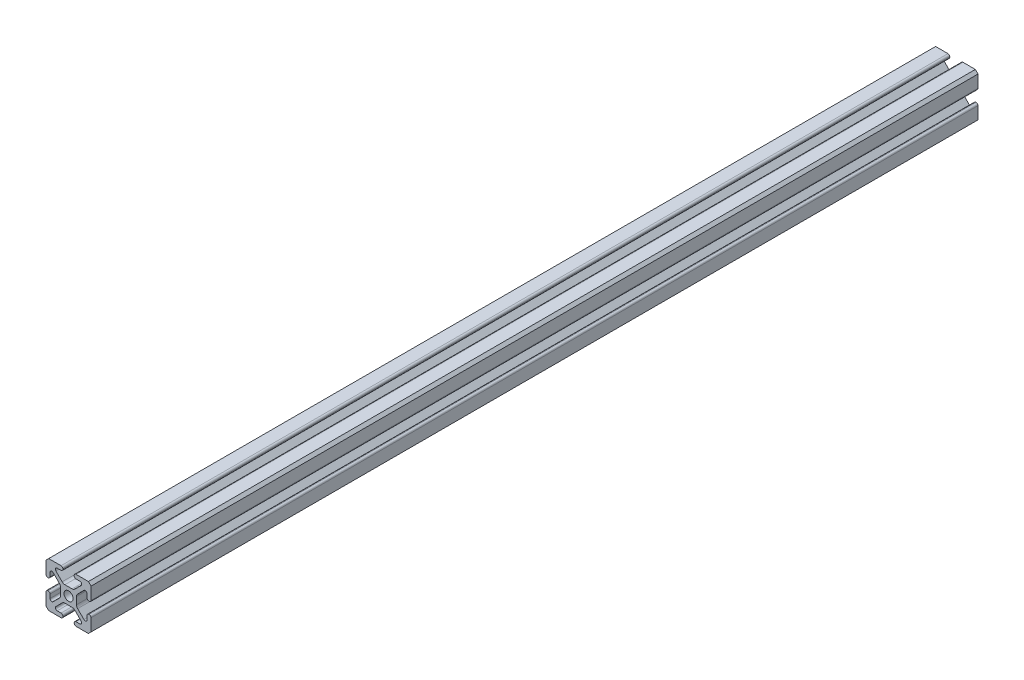
SolidWorks part; units mm, degrees
ref_plane "Front Plane" through (0, 0, 0) normal (0, 0, 1) x (1, 0, 0)
ref_plane "Top Plane" through (0, 0, 0) normal (0, 1, 0) x (1, 0, 0)
ref_plane "Right Plane" through (0, 0, 0) normal (1, 0, 0) x (0, 0, -1)
other "Configuration Table"
sketch "Sketch1" plane through (0, 0, 0) normal (0, 0, 1) x (1, 0, 0)
  line L0 (-11.2, -12.7) -> (-4.2223, -12.7)
  line L1 (-3.2063, -11.684) -> (-3.2063, -11.4407)
  line L2 (-4.2223, -10.4247) -> (-6.4093, -10.4247)
  line L3 (-7.1277, -8.6902) -> (-3.5932, -5.1557)
  line L4 (-2.0306, -4.5085) -> (2.0306, -4.5085)
  line L5 (3.5932, -5.1557) -> (7.1277, -8.6902)
  line L6 (6.4093, -10.4247) -> (4.2223, -10.4247)
  line L7 (3.2063, -11.4407) -> (3.2063, -11.684)
  line L8 (4.2223, -12.7) -> (11.2, -12.7)
  line L9 (11.2, -12.7) -> (12.7, -11.2)
  line L10 (12.7, -11.2) -> (12.7, -4.2223)
  line L11 (11.684, -3.2063) -> (11.4407, -3.2063)
  line L12 (10.4247, -4.2223) -> (10.4247, -6.4093)
  line L13 (8.6902, -7.1277) -> (5.1557, -3.5932)
  line L14 (4.5085, -2.0306) -> (4.5085, 2.0306)
  line L15 (5.1557, 3.5932) -> (8.6902, 7.1277)
  line L16 (10.4247, 6.4093) -> (10.4247, 4.2223)
  line L17 (11.4407, 3.2063) -> (11.684, 3.2063)
  line L18 (12.7, 4.2223) -> (12.7, 11.2)
  line L19 (12.7, 11.2) -> (11.2, 12.7)
  line L20 (11.2, 12.7) -> (4.2223, 12.7)
  line L21 (3.2063, 11.684) -> (3.2063, 11.4407)
  line L22 (4.2223, 10.4247) -> (6.4093, 10.4247)
  line L23 (7.1277, 8.6902) -> (3.5932, 5.1557)
  line L24 (2.0306, 4.5085) -> (-2.0306, 4.5085)
  line L25 (-3.5932, 5.1557) -> (-7.1277, 8.6902)
  line L26 (-6.4093, 10.4247) -> (-4.2223, 10.4247)
  line L27 (-3.2063, 11.4407) -> (-3.2063, 11.684)
  line L28 (-4.2223, 12.7) -> (-11.2, 12.7)
  line L29 (-11.2, 12.7) -> (-12.7, 11.2)
  line L30 (-12.7, 11.2) -> (-12.7, 4.2223)
  line L31 (-11.684, 3.2063) -> (-11.4407, 3.2063)
  line L32 (-10.4247, 4.2223) -> (-10.4247, 6.4093)
  line L33 (-8.6902, 7.1277) -> (-5.1557, 3.5932)
  line L34 (-4.5085, 2.0306) -> (-4.5085, -2.0306)
  line L35 (-5.1557, -3.5932) -> (-8.6902, -7.1277)
  line L36 (-10.4247, -6.4093) -> (-10.4247, -4.2223)
  line L37 (-11.4407, -3.2063) -> (-11.684, -3.2063)
  line L38 (-12.7, -4.2223) -> (-12.7, -11.2)
  line L39 (-12.7, -11.2) -> (-11.2, -12.7)
  arc A0 (-2.555, 0) -> (2.555, 0) centre (0, 0) ccw
  arc A1 (2.555, 0) -> (-2.555, 0) centre (0, 0) ccw
  arc A2 (-4.2223, -12.7) -> (-3.2063, -11.684) centre (-4.2223, -11.684) ccw
  arc A3 (-3.2063, -11.4407) -> (-4.2223, -10.4247) centre (-4.2223, -11.4407) ccw
  arc A4 (-7.1277, -8.6902) -> (-6.4093, -10.4247) centre (-6.4093, -9.4087) ccw
  arc A5 (-2.0306, -4.5085) -> (-3.5932, -5.1557) centre (-2.0306, -6.7183) ccw
  arc A6 (3.5932, -5.1557) -> (2.0306, -4.5085) centre (2.0306, -6.7183) ccw
  arc A7 (7.4253, -9.4087) -> (7.1277, -8.6902) centre (6.4093, -9.4087) ccw
  arc A8 (6.4093, -10.4247) -> (7.4253, -9.4087) centre (6.4093, -9.4087) ccw
  arc A9 (4.2223, -10.4247) -> (3.2063, -11.4407) centre (4.2223, -11.4407) ccw
  arc A10 (3.2063, -11.684) -> (4.2223, -12.7) centre (4.2223, -11.684) ccw
  arc A11 (12.7, -4.2223) -> (11.684, -3.2063) centre (11.684, -4.2223) ccw
  arc A12 (11.4407, -3.2063) -> (10.4247, -4.2223) centre (11.4407, -4.2223) ccw
  arc A13 (8.6902, -7.1277) -> (10.4247, -6.4093) centre (9.4087, -6.4093) ccw
  arc A14 (4.5085, -2.0306) -> (5.1557, -3.5932) centre (6.7183, -2.0306) ccw
  arc A15 (5.1557, 3.5932) -> (4.5085, 2.0306) centre (6.7183, 2.0306) ccw
  arc A16 (9.4087, 7.4253) -> (8.6902, 7.1277) centre (9.4087, 6.4093) ccw
  arc A17 (10.4247, 6.4093) -> (9.4087, 7.4253) centre (9.4087, 6.4093) ccw
  arc A18 (10.4247, 4.2223) -> (11.4407, 3.2063) centre (11.4407, 4.2223) ccw
  arc A19 (11.684, 3.2063) -> (12.7, 4.2223) centre (11.684, 4.2223) ccw
  arc A20 (4.2223, 12.7) -> (3.2063, 11.684) centre (4.2223, 11.684) ccw
  arc A21 (3.2063, 11.4407) -> (4.2223, 10.4247) centre (4.2223, 11.4407) ccw
  arc A22 (7.1277, 8.6902) -> (6.4093, 10.4247) centre (6.4093, 9.4087) ccw
  arc A23 (2.0306, 4.5085) -> (3.5932, 5.1557) centre (2.0306, 6.7183) ccw
  arc A24 (-3.5932, 5.1557) -> (-2.0306, 4.5085) centre (-2.0306, 6.7183) ccw
  arc A25 (-7.4253, 9.4087) -> (-7.1277, 8.6902) centre (-6.4093, 9.4087) ccw
  arc A26 (-6.4093, 10.4247) -> (-7.4253, 9.4087) centre (-6.4093, 9.4087) ccw
  arc A27 (-4.2223, 10.4247) -> (-3.2063, 11.4407) centre (-4.2223, 11.4407) ccw
  arc A28 (-3.2063, 11.684) -> (-4.2223, 12.7) centre (-4.2223, 11.684) ccw
  arc A29 (-12.7, 4.2223) -> (-11.684, 3.2063) centre (-11.684, 4.2223) ccw
  arc A30 (-11.4407, 3.2063) -> (-10.4247, 4.2223) centre (-11.4407, 4.2223) ccw
  arc A31 (-8.6902, 7.1277) -> (-10.4247, 6.4093) centre (-9.4087, 6.4093) ccw
  arc A32 (-4.5085, 2.0306) -> (-5.1557, 3.5932) centre (-6.7183, 2.0306) ccw
  arc A33 (-5.1557, -3.5932) -> (-4.5085, -2.0306) centre (-6.7183, -2.0306) ccw
  arc A34 (-9.4087, -7.4253) -> (-8.6902, -7.1277) centre (-9.4087, -6.4093) ccw
  arc A35 (-10.4247, -6.4093) -> (-9.4087, -7.4253) centre (-9.4087, -6.4093) ccw
  arc A36 (-10.4247, -4.2223) -> (-11.4407, -3.2063) centre (-11.4407, -4.2223) ccw
  arc A37 (-11.684, -3.2063) -> (-12.7, -4.2223) centre (-11.684, -4.2223) ccw
extrude "Boss-Extrude1" add sketch "Sketch1" along normal blind 500
equation "\"Extrusion Length\"= 24"
